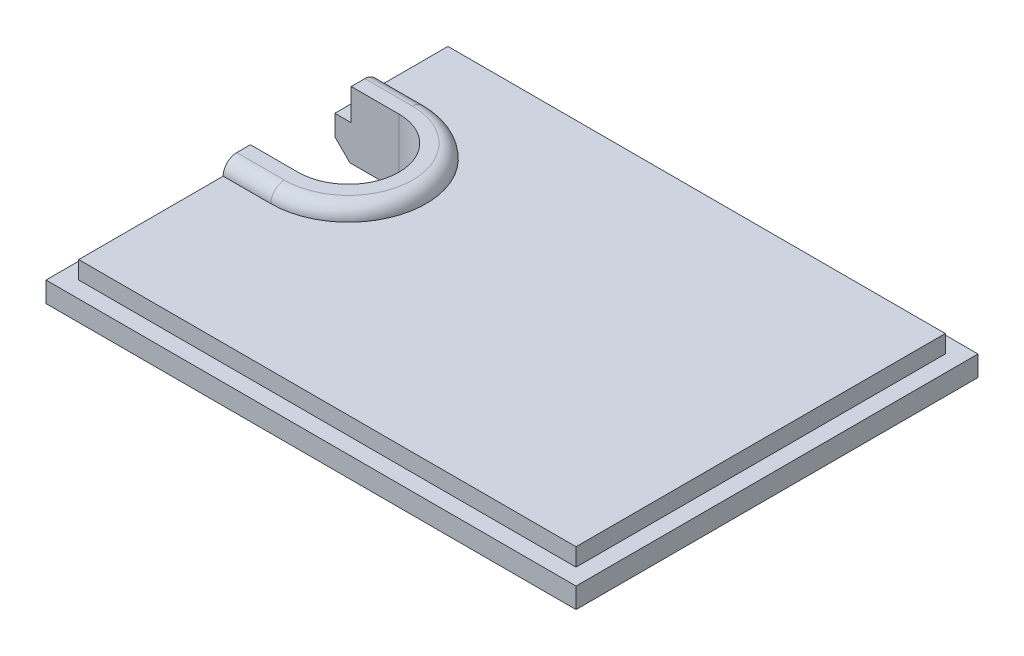
SolidWorks part; units mm, degrees
ref_plane "Front Plane" through (0, 0, 0) normal (0, 0, 1) x (1, 0, 0)
ref_plane "Top Plane" through (0, 0, 0) normal (0, 1, 0) x (1, 0, 0)
ref_plane "Right Plane" through (0, 0, 0) normal (1, 0, 0) x (0, 0, -1)
sketch "Sketch1" plane through (0, 0, 0) normal (0, 1, 0) x (1, 0, 0)
  line L0 (-19.45, 14.75) -> (-19.45, 6.45)
  line L1 (-19.45, -14.75) -> (19.45, -14.75)
  line L2 (19.45, -14.75) -> (19.45, 14.75)
  line L3 (19.45, 14.75) -> (-19.45, 14.75)
  line L4 (18.25, 13.55) -> (-18.25, 13.55)
  line L5 (-18.25, 13.55) -> (-18.25, 6.45)
  line L6 (-18.25, -13.55) -> (18.25, -13.55)
  line L7 (18.25, -13.55) -> (18.25, 13.55)
  line L8 (-18.25, 13.55) -> (0, 0) construction
  line L9 (0, 0) -> (18.25, -13.55) construction
  line L10 (0, 0) -> (18.25, 13.55) construction
  line L11 (0, 0) -> (-18.25, -13.55) construction
  line L12 (-14.75, 8.45) -> (-18.25, 8.45)
  line L13 (-18.25, 8.45) -> (-19.45, 8.45)
  line L14 (-14.75, 6.45) -> (-18.25, 6.45)
  line L15 (-18.25, 6.45) -> (-19.45, 6.45)
  line L16 (-14.75, -0.95) -> (-18.25, -0.95)
  line L17 (-18.25, -0.95) -> (-19.45, -0.95)
  line L18 (-14.75, -2.95) -> (-18.25, -2.95)
  line L19 (-18.25, -2.95) -> (-19.45, -2.95)
  line L20 (-19.45, -0.95) -> (-19.45, -14.75)
  line L21 (-19.45, 14.75) -> (-19.45, -14.75) construction
  line L22 (-18.25, -0.95) -> (-18.25, -13.55)
  line L23 (-18.25, 13.55) -> (-18.25, -13.55) construction
  arc A0 (-14.75, 6.45) -> (-14.75, -0.95) centre (-14.75, 2.75) cw
  arc A1 (-14.75, 8.45) -> (-14.75, -2.95) centre (-14.75, 2.75) cw
  arc A2 (-16.7795, 5.8437) -> (-14.75, -0.95) centre (-14.75, 2.75) cw construction
  arc A3 (-17.8766, 7.516) -> (-14.75, -2.95) centre (-14.75, 2.75) cw construction
  dimension "D4" = 3.7
  dimension "D6" = 2
  dimension "D1" = 29.5
  dimension "D2" = 38.9
  dimension "D5" = 12
  dimension "D7" = 3.5
  dimension "D3" = 1.2
extrude "Boss-Extrude1" add sketch "Sketch1" along normal blind 1 contours L12 A1 L18 L5 L6 L7 L4 | A1 L12 L5 L14 A0 L16 L18 | L19 L5 L17 L0 | L15 L5 L13 L0 | L5 L19 L0 L1 L2 L3 L13 L4 L7 L6 | L17 L20 L1 L2 L3 L0 L15 L14 A0 L16 | L4 L5 L6 L7 region at (0, 0, -14.2618) region at (-18.85, 0, -7.45) region at (-16.5, 0, -8.3035) region at (1.4336, 0, 0.2784) region at (-18.85, 0, 1.95)
extrude "Boss-Extrude2" add sketch "Sketch1<5>" along normal blind 1.6 from surface contours L5 A1 L6 L7 L4 | A1 L5 A0 | A1 L0 A0 L5 | L0 A1 L5 L4 L7 L6 L1 L2 L3 | A1 L5 A0 L0 | L5 L0 | L5 L0 | L22 L17 L20 L19 region at (0, 0, -14.2618) region at (-18.85, 0, -7.45) region at (-16.5, 0, -8.3035) region at (1.4336, 0, 0.2784) region at (-18.85, 0, 1.95) starting at face at (-8.0875, 1, -1.375)
sketch "Sketch1<5>" plane through (0, 0, 0) normal (0, 1, 0) x (1, 0, 0) same geometry as "Sketch1"
extrude "Boss-Extrude3" add sketch "Sketch1<6>" along normal blind 1.3 from surface contours L5 A1 L6 L7 L4 | A1 L5 A0 region at (-16.5, 0, -8.3035) region at (1.4336, 0, 0.2784) starting at face at (-8.0875, 2.6, -1.375)
sketch "Sketch1<6>" plane through (0, 0, 0) normal (0, 1, 0) x (1, 0, 0) same geometry as "Sketch1"
extrude "Boss-Extrude4" add sketch "Sketch1<8>" along normal blind 1 from surface contours A1 L5 A0 region at (-16.5, 0, -8.3035) starting at face at (-7.7875, 3.9, -1.375)
sketch "Sketch1<8>" plane through (0, 0, 0) normal (0, 1, 0) x (1, 0, 0) same geometry as "Sketch1"
fillet "Fillet1" radius 1 3 edges at (-9.05, 4.9, -2.75) (-16.5, 4.9, 2.95) (-16.5, 4.9, -8.45)
chamfer "Chamfer1" distance 1.1 angle 45 4 edges at (0, 0, -14.75) (19.45, 0, 0) (0, 0, 14.75) (-19.45, 0, -10.6)
